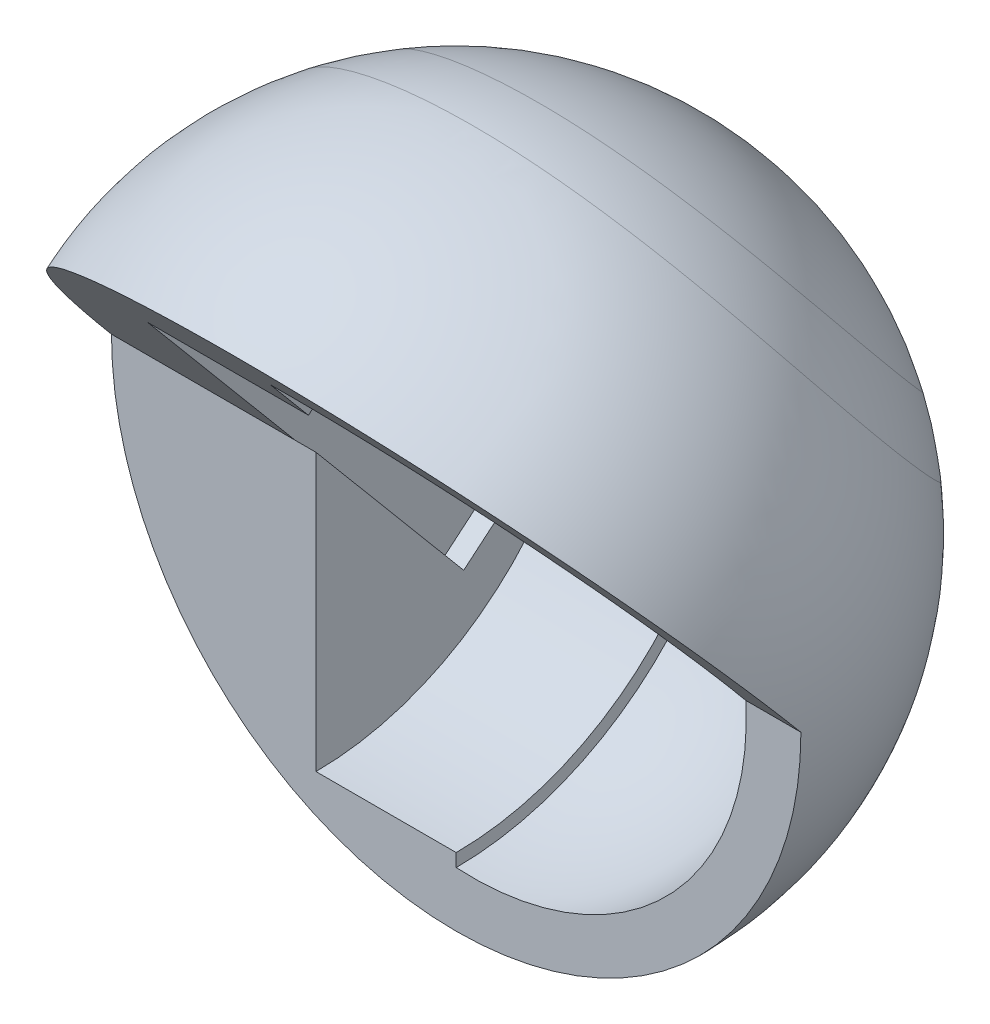
SolidWorks part; units mm, degrees
ref_plane "Front Plane" through (0, 0, 0) normal (0, 0, 1) x (1, 0, 0)
ref_plane "Top Plane" through (0, 0, 0) normal (0, 1, 0) x (1, 0, 0)
ref_plane "Right Plane" through (0, 0, 0) normal (1, 0, 0) x (0, 0, -1)
ref_axis "Axis1" through (0, 29.5432, 0) along (0, -1, 0)
sketch "Sketch3" plane through (0, 0, 0) normal (0, 0, 1) x (1, 0, 0)
  line L5 (19.05, 0) -> (-19.05, 0)
  arc A1 (-19.05, 0) -> (0, -19.05) centre (0, 0) ccw
  arc A2 (19.05, 0) -> (0, -19.05) centre (0, 0) cw
revolve "Revolve4" add sketch "Sketch3" angle 220 about L5 reverse direction yes
sketch "Sketch10" plane through (0, 0, 0) normal (0, -0.6428, 0.766) x (1, 0, 0)
  line L1 (0, 0) -> (0, 16.002)
  line L2 (0, 0) -> (16.002, 0)
  line L3 (19.05, 0) -> (-19.05, 0) construction
  arc A3 (16.002, 0) -> (0, 16.002) centre (0.8908, 0.8908) ccw
  arc A4 (19.05, 0) -> (-19.05, 0) centre (0, 0) ccw construction
  point P4 (0, 0)
  point P14 (0, 19.05)
  dimension "D1" = 3.048
  dimension "D2" = 3.048
revolve "Cut-Revolve1" cut sketch "Sketch10" angle 234 about L2 reverse direction yes
sketch "Sketch11" plane through (0, 0, 0) normal (0, -0.6428, 0.766) x (1, 0, 0)
  line L11 (0, 12.7) -> (-8.89, 12.7)
  line L12 (0, 12.7) -> (0, -12.7)
  line L13 (0, -12.7) -> (-8.89, -12.7)
  line L14 (-8.89, 12.7) -> (-8.89, -12.7)
  point P4 (0, 0)
  dimension "D1" = 25.4
  dimension "D2" = 8.89
extrude "Cut-Extrude3" cut sketch "Sketch11" against normal blind 10.16
sketch "Sketch12" plane through (0, 0, 0) normal (0, 0, 1) x (1, 0, 0)
  line L0 (-7.7494, 0) -> (-7.7494, -15.2811)
  line L1 (0, 0) -> (-7.7494, 0)
  line L2 (0, 0) -> (0, -15.2811)
  line L3 (0, -15.2811) -> (-7.7494, -15.2811)
revolve "Cut-Revolve2" cut sketch "Sketch12" angle 59 about axis through (19.05, 0, 0) along (-1, 0, 0) reverse direction yes
ref_plane "Plane1" through (0, 12.2451, -14.5931) normal (0, -0.6428, 0.766) x (1, 0, 0)
sketch "Sketch15" plane through (0, 12.2451, -14.5931) normal (0, -0.6428, 0.766) x (1, 0, 0)
  ellipse E0 centre (0, 0) end of major axis (-15.24, 0) minor radius 13.97
  ellipse E1 centre (0, 0) end of major axis (-12.691, 0.4772) minor radius 11.43
curve "Curve2"
curve "Curve3"
sketch "Sketch15<4>" plane through (0, 12.2451, -14.5931) normal (0, -0.6428, 0.766) x (1, 0, 0) same geometry as "Sketch15"
split line "Split Line1"
sketch "Sketch15<5>" plane through (0, 12.2451, -14.5931) normal (0, -0.6428, 0.766) x (1, 0, 0) same geometry as "Sketch15"
